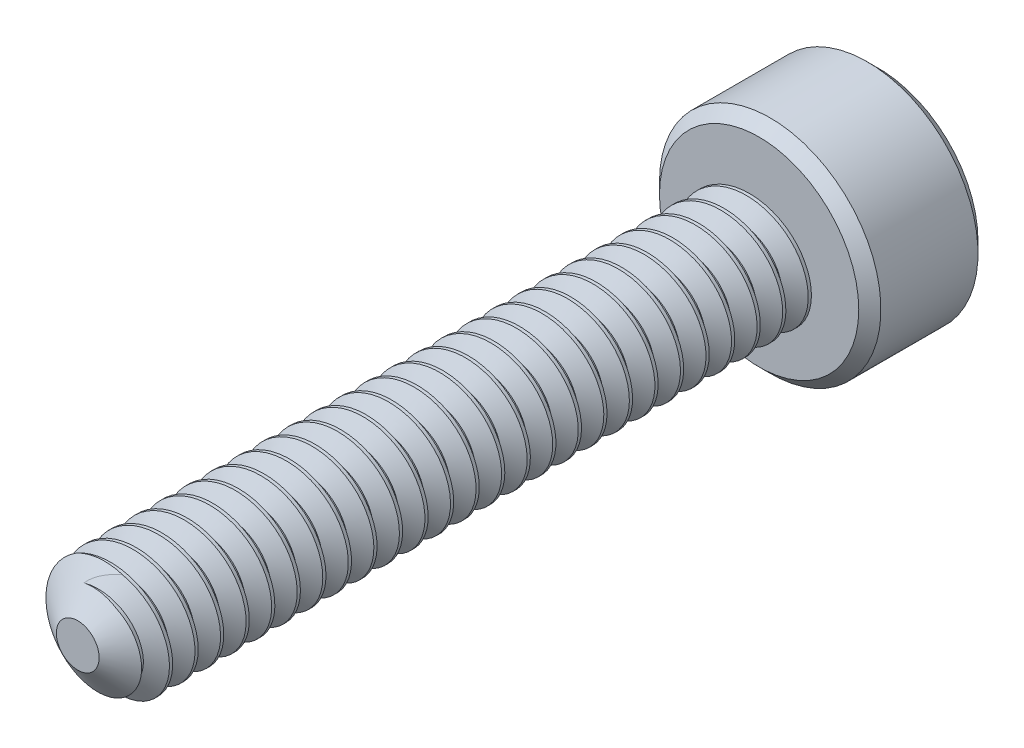
SolidWorks part; units mm, degrees
other "DetailItem1"
ref_plane "Front Plane" through (0, 0, 0) normal (0, 0, 1) x (1, 0, 0)
ref_plane "Top Plane" through (0, 0, 0) normal (0, 1, 0) x (1, 0, 0)
ref_plane "Right Plane" through (0, 0, 0) normal (1, 0, 0) x (0, 0, -1)
sketch "Sketch1" plane through (0, 0, 0) normal (0, 0, 1) x (1, 0, 0)
  circle A0 centre (0, 0) radius 0.7
  dimension "OD" = 1.4
extrude "Extrude1" add sketch "Sketch1" against normal blind 8
sketch "Sketch2" plane through (0, 0, 0) normal (0, 0, 1) x (1, 0, 0)
  circle A0 centre (0, 0) radius 0.7 construction
  circle A1 centre (0, 0) radius 0.7
curve "Helix/Spiral1" pitch 0.3 height 8.3 radius 0.7 centre (0, 0, 0) axis (0, 0, -1) start towards (0, 1, 0) parameters "pitch"=0.3
sketch "Sketch3" plane through (0, 0, 0) normal (1, 0, 0) x (0, 0, -1)
  line L0 (-0.2625, 0.7) -> (-0.15, 0.5051)
  line L1 (-0.15, 0.5051) -> (-0.1125, 0.5051)
  line L2 (-0.1125, 0.5051) -> (0, 0.7)
  line L3 (-0.2625, 0.7) -> (0, 0.7)
  line L4 (-0.1312, 0.7) -> (-0.1313, 0.5051) construction
  line L5 (-0.2062, 0.6026) -> (-0.0563, 0.6026) construction
  line L6 (0, 0.7) -> (0, -0.7) construction
  dimension "D1" = 0.0375
  dimension "D2" = 0.15
  dimension "D3" = 60
sweep "Cut-Sweep1" cut profiles "Sketch3" path "Helix/Spiral1" align with end faces yes
sketch "Sketch4" plane through (0, 0, 0) normal (1, 0, 0) x (0, 0, -1)
  line L0 (0.3143, 0.7) -> (0, 0.2511)
  line L1 (0, 0.2511) -> (0, 0.7)
  line L2 (0.3143, 0.7) -> (0, 0.7)
  line L3 (-0.2625, 0.7) -> (0, 0.7) construction
  line L4 (0, 0) -> (7.0209, 0) construction
  dimension "D1" = 55
  dimension "D2" = 0.254
revolve "Cut-Revolve1" cut sketch "Sketch4" angle 360 about L4
sketch "Sketch6" plane through (0, 0, -8) normal (0, 0, -1) x (-1, 0, 0)
  circle A0 centre (0, 0) radius 1.3
  dimension "head dia" = 2.6
extrude "Extrude2" add sketch "Sketch6" along normal blind 1.4
sketch "Sketch7" plane through (0, 0, -9.4) normal (0, 0, -1) x (-1, 0, 0)
  line L1 (0, 0.7506) -> (-0.65, 0.3753)
  line L2 (-0.65, 0.3753) -> (-0.65, -0.3753)
  line L3 (-0.65, -0.3753) -> (0, -0.7506)
  line L4 (0, -0.7506) -> (0.65, -0.3753)
  line L5 (0.65, -0.3753) -> (0.65, 0.3753)
  line L6 (0.65, 0.3753) -> (0, 0.7506)
  circle A0 centre (0, 0) radius 0.65 construction
  dimension "hex dia" = 1.3
extrude "Cut-Extrude1" cut sketch "Sketch7" against normal blind 0.975
sketch "Sketch8" plane through (0, 0, -9.4) normal (0, 0, -1) x (-1, 0, 0)
  circle A0 centre (0, 0) radius 0.7506
extrude "Cut-Extrude2" cut sketch "Sketch8" against normal through all draft 45
chamfer "Chamfer1" distance 0.13 angle 45 2 edges at (-1.3, 0, -9.4) (-1.3, 0, -8)
sketch "Sketch10" plane through (0, 0, -8) normal (0, 0, 1) x (1, 0, 0)
  circle A1 centre (0, 0) radius 0.7
  circle A2 centre (0, 0) radius 0.7
  dimension "D1" = 0
ref_plane "Plane1" through (0, 0, -22) normal (0, 0, 1) x (1, 0, 0)
extrude "partial thread" [suppressed] add sketch "Sketch10" along normal up to surface (58 mm away) separate body
chamfer "Chamfer2" [suppressed] distance 0.028 angle 45
combine bodies "Combine1" [suppressed] operation type add bodies to combine 107 108
sketch "Sketch9" plane through (0, 0, 0) normal (1, 0, 0) x (0, 0, -1)
  line L0 (0, 0.7) -> (0, -0.7) construction
  line L1 (0.75, 0.7) -> (0.75, -0.7) construction
  dimension "D1" = 0.75
equation "\"D3@Helix/Spiral1\" = \"screw length@Extrude1\"+\"pitch@Helix/Spiral1\""
equation "\"D1@Sketch3\" = \"pitch@Helix/Spiral1\"*.125"
equation "\"D2@Sketch3\" = \"pitch@Helix/Spiral1\"*.5"
equation "\"D1@Cut-Extrude1\" = \"hex dia@Sketch7\"*.75"
equation "\"D1@Chamfer1\" = \"head dia@Sketch6\"*.05"
equation "\"D1@Sketch9\" = \"pitch@Helix/Spiral1\"*2.5"
equation "\"D1@Chamfer2\"=\"OD@Sketch1\"*.02"
